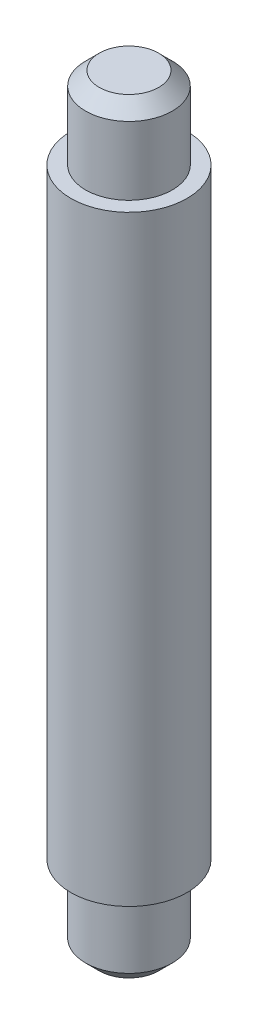
SolidWorks part; units mm, degrees
ref_plane "Front Plane" through (0, 0, 0) normal (0, 0, 1) x (1, 0, 0)
ref_plane "Top Plane" through (0, 0, 0) normal (0, 1, 0) x (1, 0, 0)
ref_plane "Right Plane" through (0, 0, 0) normal (1, 0, 0) x (0, 0, -1)
sketch "Sketch5" plane through (0, 0, 0) normal (0, 1, 0) x (1, 0, 0)
  circle A0 centre (0, 0) radius 3.175
  circle A1 centre (0, 0) radius 4.25
  dimension "D1" = 8.5
  dimension "D2" = 6.35
extrude "Boss-Extrude10" add sketch "Sketch5" along normal blind 56 contours A0 region at (0, 0, 0)
extrude "Boss-Extrude11" add sketch "Sketch5<3>" along normal blind 44 from offset 6
sketch "Sketch5<3>" plane through (0, 0, 0) normal (0, 1, 0) x (1, 0, 0) same geometry as "Sketch5"
chamfer "Chamfer4" distance 1 angle 45 2 edges at (0, 0, 3.175) (0, 56, 3.175)
